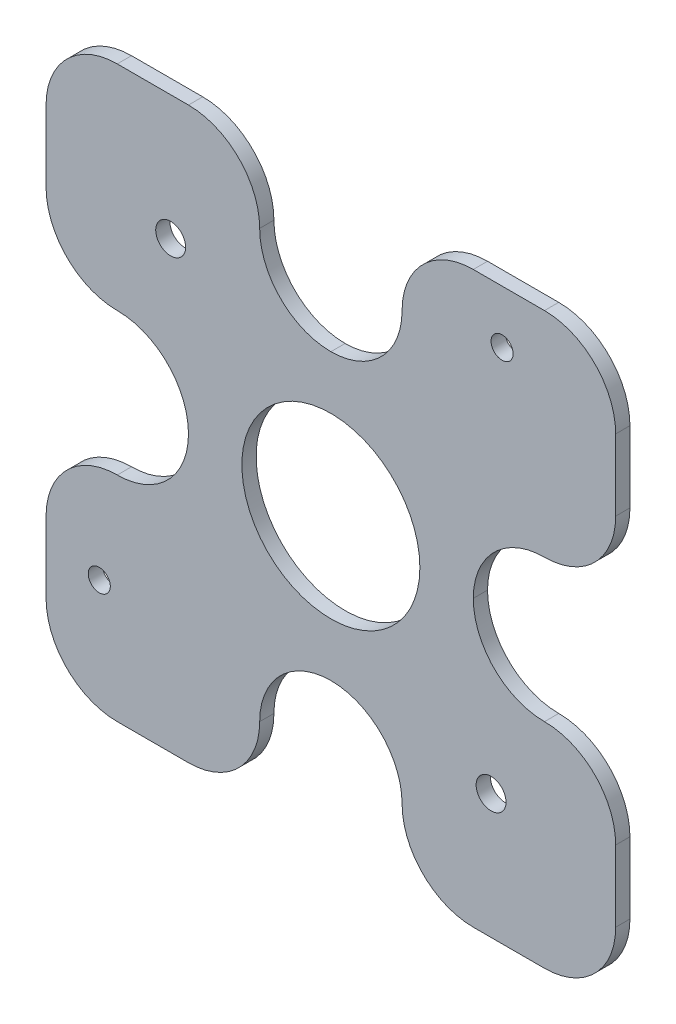
SolidWorks part; units mm, degrees
ref_plane "前视基准面" through (0, 0, 0) normal (0, 0, 1) x (1, 0, 0)
ref_plane "上视基准面" through (0, 0, 0) normal (0, 1, 0) x (1, 0, 0)
ref_plane "右视基准面" through (0, 0, 0) normal (1, 0, 0) x (0, 0, -1)
other "Configuration Table"
sketch "草图1" plane through (0, 0, 0) normal (0, 0, 1) x (1, 0, 0)
  line L0 (40, 0) -> (40, 15.986) construction
  line L1 (0, 0) -> (80, 0)
  line L2 (0, 0) -> (0, 80)
  line L3 (0, 80) -> (80, 80)
  line L4 (80, 0) -> (80, 80)
  line L5 (80, 40) -> (65.6079, 40) construction
  line L7 (80, 80) -> (0, 0) construction
  line L8 (17.5, 17.5) -> (62.5, 17.5) construction
  line L11 (0, 8.4853) -> (71.5147, 80) construction
  line L12 (40, 40) -> (35.7574, 44.2426) construction
  circle A5 centre (17.5, 62.5) radius 2.1
  circle A6 centre (62.5, 62.5) radius 2.1 construction
  circle A7 centre (62.5, 17.5) radius 2.1
  circle A8 centre (17.5, 17.5) radius 2.1 construction
  circle A13 centre (7.4731, 15.9584) radius 1.55
  circle A14 centre (64.0416, 72.5269) radius 1.55
  point P5 (40, 40)
  point P6 (35.7574, 44.2426)
  point P21 (40, 40)
  point P30 (40, 40)
  point P34 (40, 40)
  dimension "D7" = 4.2
  dimension "D8" = 45
  dimension "D13" = 3.1
  dimension "D14" = 80
  dimension "D1" = 80
  dimension "D2" = 80
  dimension "D12" = 6
  dimension "D6" = 4
extrude "凸台-拉伸1" add sketch "草图1" along normal blind 2
sketch "草图2" plane through (0, 0, 2) normal (0, 0, 1) x (1, 0, 0)
  line L1 (0, 40) -> (29.5395, 40) construction
  line L2 (0, 80) -> (0, 0) construction
  line L3 (80, 80) -> (0, 80) construction
  line L4 (30, 60) -> (50, 60)
  line L5 (30, 60) -> (30, 80)
  line L6 (30, 80) -> (50, 80)
  line L7 (50, 60) -> (50, 80)
  line L8 (30, 60) -> (50, 80) construction
  line L9 (30, 80) -> (50, 60) construction
  line L10 (40, 47.0711) -> (40, 32.9289) construction
  line L11 (60, 50) -> (80, 50)
  line L12 (60, 50) -> (60, 30)
  line L13 (60, 30) -> (80, 30)
  line L14 (80, 50) -> (80, 30)
  line L15 (50, 20) -> (50, 0)
  line L16 (50, 20) -> (30, 20)
  line L17 (30, 20) -> (30, 0)
  line L18 (50, 0) -> (30, 0)
  line L19 (20, 30) -> (0, 30)
  line L20 (20, 30) -> (20, 50)
  line L21 (20, 50) -> (0, 50)
  line L22 (0, 30) -> (0, 50)
  point P0 (40, 40)
  point P2 (0, 0)
  point P3 (0, 0)
  point P8 (40, 70)
  point P19 (40, 40)
  point P35 (40, 40)
  dimension "D1" = 20
  dimension "D2" = 20
  dimension "D3" = 4
extrude "切除-拉伸1" cut sketch "草图2" against normal blind 2
fillet "圆角1" radius 10 20 edges at (0, 50, 1) (20, 50, 1) (20, 30, 1) (0, 30, 1) (0, 0, 1) (30, 0, 1) (30, 20, 1) (50, 20, 1) (50, 0, 1) (80, 0, 1) (80, 30, 1) (60, 30, 1) (60, 50, 1) (80, 50, 1) (80, 80, 1) (50, 80, 1) (50, 60, 1) (30, 60, 1) (30, 80, 1) (0, 80, 1)
sketch "草图3" plane through (0, 0, 2) normal (0, 0, 1) x (1, 0, 0)
  line L0 (40, 60) -> (40, 40) construction
  line L1 (60, 40) -> (40, 40) construction
  circle A0 centre (40, 40) radius 12.5
  arc A1 (60, 40) -> (70, 30) centre (70, 40) ccw construction
  point P3 (39.6432, 40)
  point P12 (40, 39.675)
  dimension "D1" = 25
extrude "切除-拉伸2" cut sketch "草图3" against normal blind 2
